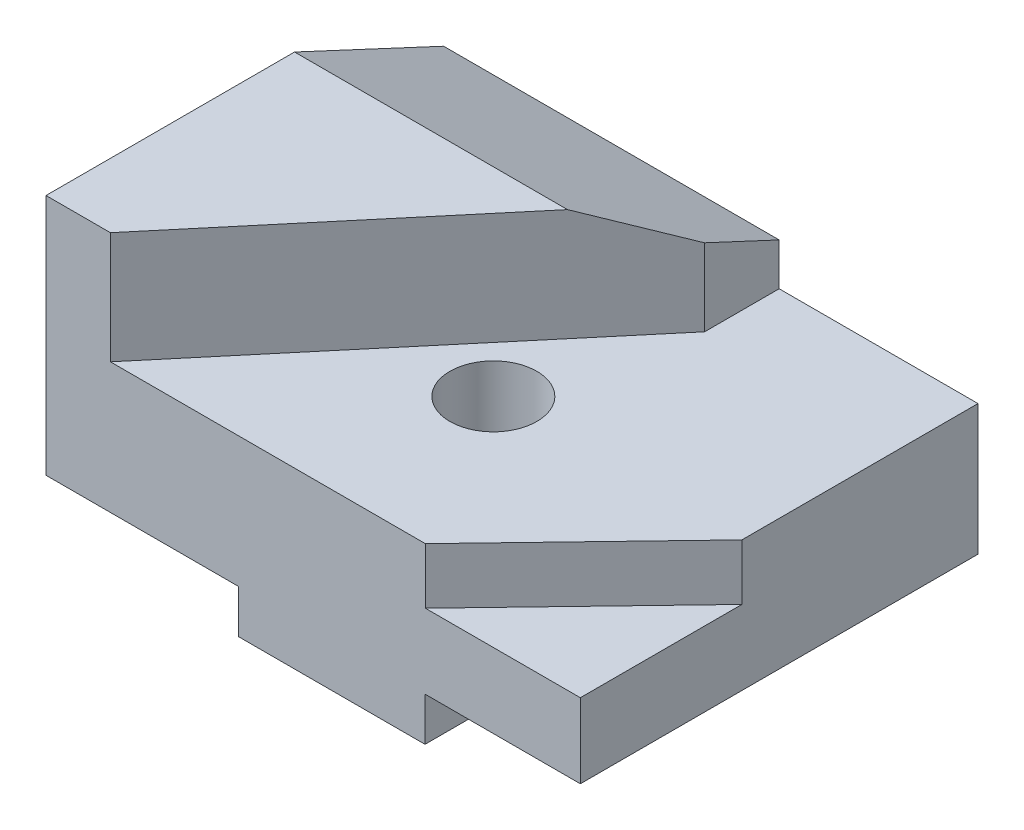
SolidWorks part; units mm, degrees
ref_plane "Front Plane" through (0, 0, 0) normal (0, 0, 1) x (1, 0, 0)
ref_plane "Top Plane" through (0, 0, 0) normal (0, 1, 0) x (1, 0, 0)
ref_plane "Right Plane" through (0, 0, 0) normal (1, 0, 0) x (0, 0, -1)
sketch "Sketch1" plane through (0, 0, 0) normal (0, 0, 1) x (1, 0, 0)
  line L0 (0, 0) -> (0, 39)
  line L1 (0, 39) -> (54, 39)
  line L2 (54, 39) -> (54, 21)
  line L3 (54, 21) -> (86, 21)
  line L6 (86, 21) -> (86, 0)
  line L7 (86, 0) -> (61, 0)
  line L8 (61, 0) -> (61, -7)
  line L9 (61, -7) -> (31, -7)
  line L10 (31, -7) -> (31, 0)
  line L11 (31, 0) -> (0, 0)
  point P6 (86, 21)
  point P10 (86, 20.6415)
  dimension "D1" = 39
  dimension "D2" = 7
  dimension "D3" = 31
  dimension "D4" = 25
  dimension "D5" = 86
  dimension "D7" = 18
  dimension "D8" = 32
extrude "Boss-Extrude1" add sketch "Sketch1" against normal blind 64
sketch "Sketch3" plane through (54, 0, 0) normal (1, 0, 0) x (0, 0, -1)
  line L0 (64, 27.8086) -> (40, 39)
  line L1 (64, 21) -> (64, 39) construction
  line L2 (64, 39) -> (0, 39) construction
  line M6 (64, 21) -> (64, 39)
  line M7 (64, 39) -> (0, 39)
  dimension "D3" = 24
  dimension "D4" = 25
extrude "Cut-Extrude1" cut sketch "Sketch3" against normal through all contours L0 M6 M7 region at (54, 35.2695, -56)
sketch "Sketch4" plane through (0, 39, 0) normal (0, 1, 0) x (1, 0, 0)
  line L0 (54, 52) -> (10.3668, 0)
  line L1 (54, 64) -> (54, 40) construction
  line L2 (54, 0) -> (0, 0) construction
  line L3 (61, 64) -> (61, 0) construction
  line L4 (54, 52) -> (54, 0)
  line L5 (54, 0) -> (10.3668, 0)
  line L6 (0, 40) -> (0, 0) construction
  line L8 (86, 26) -> (86, -0.0579)
  line L9 (86, -0.0579) -> (61, -0.0579)
  line L17 (86, 64) -> (54, 64) construction
  line L18 (86, 26) -> (61, -0.0579)
  line L19 (86, 64) -> (86, 0) construction
  line L20 (86, 0) -> (54, 0) construction
  circle A0 centre (46, 26) radius 7
  point P16 (0, 0)
  line M2 (54, 40) -> (0, 40)
  line M4 (0, 0) -> (54, 0)
  line M5 (54, 0) -> (54, 40)
  dimension "D3" = 14
  dimension "D1" = 40
  dimension "D2" = 12
  dimension "D4" = 46
  dimension "D5" = 26
  dimension "D6" = 26
  dimension "D7" = 18
extrude "Cut-Extrude2" cut sketch "Sketch4" against normal blind 18 contours L4 L0 M2 | L0 A0 M2 M4 M5
extrude "Cut-Extrude7" cut sketch "Sketch4<6>" against normal up to next contours A0 region at (46, 39, -26)
sketch "Sketch4<6>" plane through (0, 39, 0) normal (0, 1, 0) x (1, 0, 0) same geometry as "Sketch4"
extrude "Cut-Extrude8" cut sketch "Sketch4<7>" against normal blind 9 from offset 18 contours L8 L18 L9 region at (77.6667, 39, -8.6281) offset against normal yes
sketch "Sketch4<7>" plane through (0, 39, 0) normal (0, 1, 0) x (1, 0, 0) same geometry as "Sketch4"
